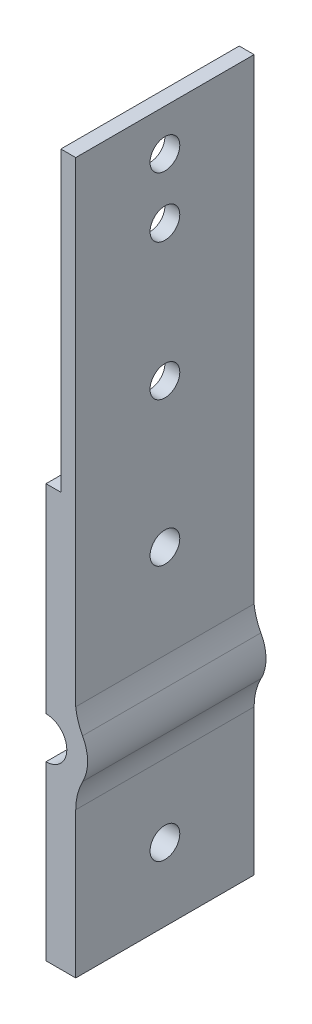
SolidWorks part; units mm, degrees
ref_plane "Front Plane" through (0, 0, 0) normal (0, 0, 1) x (1, 0, 0)
ref_plane "Top Plane" through (0, 0, 0) normal (0, 1, 0) x (1, 0, 0)
ref_plane "Right Plane" through (0, 0, 0) normal (1, 0, 0) x (0, 0, -1)
sketch "Sketch1" plane through (0, 0, 0) normal (0, 0, 1) x (1, 0, 0)
  circle A0 centre (0, 0) radius 2.5
  circle A1 centre (0, 0) radius 7
extrude "Boss-Extrude1" add sketch "Sketch1" along normal blind 30
sketch "Sketch2" plane through (0, 0, 30) normal (0, 0, 1) x (1, 0, 0)
  line L1 (0, 7) -> (5, 7)
  line L2 (0, 7) -> (0, 87)
  line L3 (0, 87) -> (5, 87)
  line L4 (5, 7) -> (5, 87)
  circle A0 centre (0, 0) radius 7 construction
  dimension "D1" = 80
  dimension "D2" = 5
extrude "Boss-Extrude2" add sketch "Sketch2" against normal blind 30 separate body
sketch "Sketch3" plane through (0, 0, 30) normal (0, 0, 1) x (1, 0, 0)
  line L0 (0, 87) -> (0, 7) construction
  line L1 (0, 9.1519) -> (4.9934, 9.1519)
  line L2 (0, 9.1519) -> (0, 3.294)
  line L3 (0, 3.294) -> (4.9934, 3.294)
  line L4 (4.9934, 9.1519) -> (4.9934, 3.294)
extrude "Boss-Extrude3" add sketch "Sketch3" against normal blind 30
fillet "Fillet1" radius 10 1 edges at (4.9934, 4.9057, 15)
sketch "Sketch4" plane through (5, 0, 0) normal (1, 0, 0) x (0, 0, -1)
  line L0 (-15, 7) -> (-15, 87) construction
  line L1 (0, 7) -> (-30, 7) construction
  line L2 (0, 87) -> (-30, 87) construction
  circle A0 centre (-15, 22.7617) radius 2.5
  circle A1 centre (-15, 47) radius 2.5
  circle A2 centre (-15, 69.9539) radius 2.5
  circle A3 centre (-15, 80.0478) radius 2.5
  dimension "D1" = 5
  dimension "D2" = 5
extrude "Cut-Extrude1" cut sketch "Sketch4" against normal blind 30
sketch "Sketch5" plane through (0, 0, 0) normal (0, 0, -1) x (-1, 0, 0)
  line L0 (0, 87) -> (0, 7) construction
  line L1 (0, 7) -> (18.4836, 7)
  line L2 (0, 7) -> (0, -8.5686)
  line L3 (0, -8.5686) -> (18.4836, -8.5686)
  line L4 (18.4836, 7) -> (18.4836, -8.5686)
  arc A0 (-6.1473, 3.3482) -> (0, 7) centre (0, 0) ccw construction
extrude "Cut-Extrude2" cut sketch "Sketch5" against normal blind 30
sketch "Sketch6" plane through (0, 0, 0) normal (-1, 0, 0) x (0, 0, 1)
  line L1 (0, -2.5) -> (30, -2.5)
  line L2 (0, -2.5) -> (0, -32.5)
  line L3 (0, -32.5) -> (30, -32.5)
  line L4 (30, -2.5) -> (30, -32.5)
  dimension "D1" = 30
extrude "Boss-Extrude4" add sketch "Sketch6" against normal blind 5
fillet "Fillet2" radius 10 1 edges at (5, -4.899, 15)
sketch "Sketch7" plane through (5, 0, 0) normal (1, 0, 0) x (0, 0, -1)
  line L0 (-15, -8) -> (-15, -32.5) construction
  line L1 (0, -8) -> (-30, -8) construction
  line L2 (0, -32.5) -> (-30, -32.5) construction
  circle A0 centre (-15, -20.25) radius 2.5
extrude "Cut-Extrude3" cut sketch "Sketch7" against normal blind 5
sketch "Sketch8" plane through (0, 0, 0) normal (0, 0, -1) x (-1, 0, 0)
  circle A0 centre (0, 0) radius 3.5
  dimension "D1" = 7
extrude "Cut-Extrude4" cut sketch "Sketch8" against normal blind 45
sketch "Sketch9" plane through (0, 0, 0) normal (0, 0, -1) x (-1, 0, 0)
  line L1 (0, 87) -> (-2.5, 87)
  line L2 (0, 87) -> (0, 37)
  line L3 (0, 37) -> (-2.5, 37)
  line L4 (-2.5, 87) -> (-2.5, 37)
  dimension "D1" = 2.5
  dimension "D2" = 50
extrude "Cut-Extrude5" cut sketch "Sketch9" against normal blind 50
